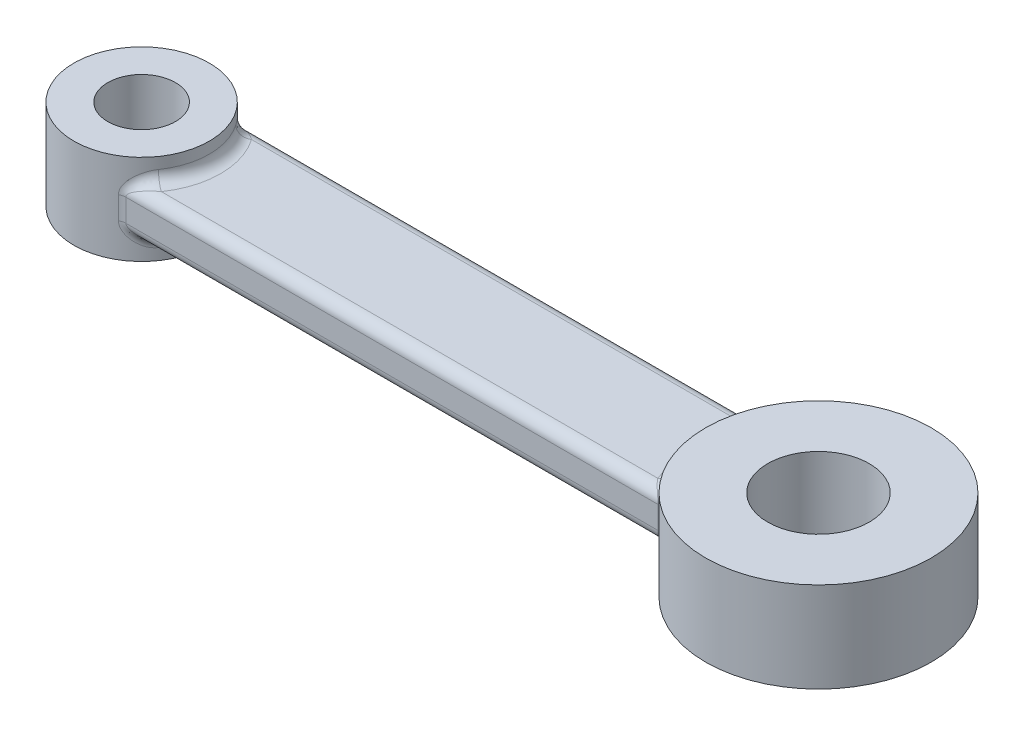
SolidWorks part; units mm, degrees
ref_plane "Front Plane" through (0, 0, 0) normal (0, 0, 1) x (1, 0, 0)
ref_plane "Top Plane" through (0, 0, 0) normal (0, 1, 0) x (1, 0, 0)
ref_plane "Right Plane" through (0, 0, 0) normal (1, 0, 0) x (0, 0, -1)
sketch "Sketch1" plane through (0, 0, 0) normal (0, 1, 0) x (1, 0, 0)
  line L1 (0, 0) -> (30, 0)
  line L2 (0, 0) -> (0, 5)
  line L3 (0, 5) -> (30, 5)
  line L4 (30, 0) -> (30, 5)
  dimension "D1" = 5
  dimension "D2" = 30
extrude "Boss-Extrude1" add sketch "Sketch1" along normal mid plane 2 contours L3 L4 L1 L2
sketch "Sketch3" plane through (0, 0, 0) normal (0, 1, 0) x (1, 0, 0)
  line L0 (30, 0) -> (30, 5) construction
  line L1 (0, 0) -> (0, 5) construction
  circle A0 centre (0, 2.5) radius 3
  circle A1 centre (30, 2.5) radius 5
  point P6 (30, 2.5)
  point P9 (0, 2.5)
  dimension "D1" = 10
  dimension "D2" = 6
extrude "Boss-Extrude3" add sketch "Sketch3" along normal mid plane 4
sketch "Sketch4" plane through (0, 2, 0) normal (0, 1, 0) x (1, 0, 0)
  line L0 (0, -0.5) -> (0, 5.5) construction
  line L1 (30, -2.5) -> (30, 7.5) construction
  circle A0 centre (0, 2.5) radius 1.5
  circle A1 centre (0, 2.5) radius 3 construction
  circle A2 centre (30, 2.5) radius 5 construction
  circle A3 centre (30, 2.5) radius 2.25
  point P8 (0, 2.5)
  dimension "D1" = 3
  dimension "D2" = 4.5
extrude "Cut-Extrude1" cut sketch "Sketch4" against normal blind 4 contours A3 | A0
fillet "Fillet1" radius 0.5 1 edges at (13.6641, 1, 0)
fillet "Fillet2" radius 0.5 1 edges at (13.6641, 1, -5)
fillet "Fillet3" radius 0.5 1 edges at (13.6641, -1, -5)
fillet "Fillet4" radius 0.5 1 edges at (13.6641, -1, 0)
fillet "Fillet5" radius 0.5 16 edges at (1.7238, 0.7066, -0.0447) (1.6583, 0, 0) (1.8019, -0.8019, -0.1014) (3, -1, -2.5) (1.7238, -0.7066, -4.9553) (1.6583, 0, -5) (1.8019, 0.8019, -4.8986) (25.6204, 0.7829, -4.9123) (25.6699, 0, -5) (25.5801, -0.8688, -4.8376) (25, -1, -2.5) (25.6204, -0.7829, -0.0877) (25.6699, 0, 0) (25.5801, 0.8688, -0.1624) (3, 1, -2.5) (25, 1, -2.5)
